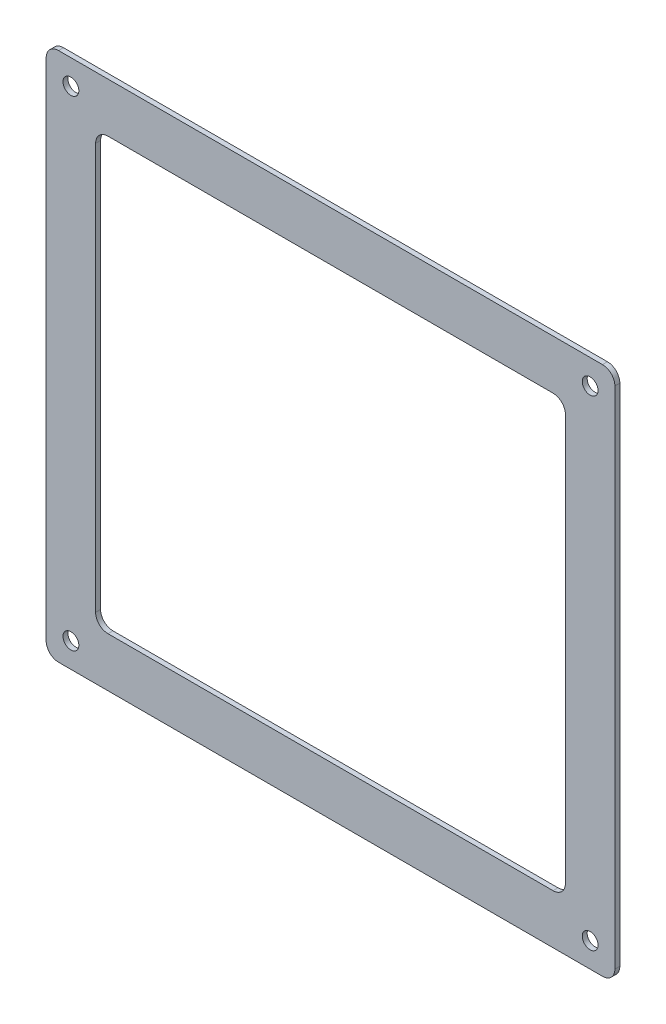
SolidWorks part; units mm, degrees
ref_plane "前视基准面" through (0, 0, 0) normal (0, 0, 1) x (1, 0, 0)
ref_plane "上视基准面" through (0, 0, 0) normal (0, 1, 0) x (1, 0, 0)
ref_plane "右视基准面" through (0, 0, 0) normal (1, 0, 0) x (0, 0, -1)
sketch "草图1" plane through (0, 0, 0) normal (0, 0, 1) x (1, 0, 0)
  line L1 (95, -87.125) -> (-95, -87.125)
  line L2 (95, -87.125) -> (95, 87.125)
  line L3 (95, 87.125) -> (-95, 87.125)
  line L4 (-95, -87.125) -> (-95, 87.125)
  line L5 (95, -87.125) -> (-95, 87.125) construction
  line L6 (95, 87.125) -> (-95, -87.125) construction
  line L7 (115, -107.125) -> (-115, -107.125)
  line L8 (115, -107.125) -> (115, 107.125)
  line L9 (115, 107.125) -> (-115, 107.125)
  line L10 (-115, -107.125) -> (-115, 107.125)
  line L11 (115, -107.125) -> (-115, 107.125) construction
  line L12 (115, 107.125) -> (-115, -107.125) construction
  point P0 (0, 0)
  point P6 (0, 0)
  dimension "D1" = 20
  dimension "D2" = 20
  dimension "D3" = 174.25
  dimension "D4" = 190
extrude "凸台-拉伸1" add sketch "草图1" along normal blind 2
fillet "圆角1" radius 5 8 edges at (95, -87.125, 1) (95, 87.125, 1) (-115, -107.125, 1) (-95, -87.125, 1) (-115, 107.125, 1) (-95, 87.125, 1) (115, -107.125, 1) (115, 107.125, 1)
sketch "草图2" plane through (0, 0, 2) normal (0, 0, 1) x (1, 0, 0)
  line L0 (-115, 102.125) -> (-115, -102.125) construction
  line L1 (110, 107.125) -> (-110, 107.125) construction
  line L2 (115, -102.125) -> (115, 102.125) construction
  line L3 (-110, -107.125) -> (110, -107.125) construction
  point P0 (-105, 97.125)
  point P1 (-105, -97.125)
  point P2 (105, -97.125)
  point P3 (105, 97.125)
  dimension "D1" = 10
  dimension "D2" = 10
  dimension "D3" = 10
  dimension "D4" = 10
  dimension "D5" = 10
  dimension "D6" = 10
  dimension "D7" = 10
  dimension "D8" = 10
hole_wizard "Ø6.4 (6.4) 直径孔1" positions "草图3" profile "草图4" hole size "Ø6.4" standard "GB" end condition through all
sketch "草图3" plane through (0, 0, 2) normal (0, 0, 1) x (1, 0, 0)
  point P0 (-105, 97.125)
  point P3 (-105, -97.125)
  point P6 (105, -97.125)
  point P9 (105, 97.125)
sketch "草图4" plane through (-105, 97.125, 2) normal (1, 0, 0) x (0, -1, 0)
  line L0 (0, 0) -> (0, 2)
  line L1 (0, 2) -> (3.2, 2)
  line L2 (3.2, 2) -> (3.2, 0)
  line L5 (3.2, 0) -> (0, 0)
  line L11 (0, -6.35) -> (0, 107.95) construction
  dimension "通孔孔直径" = 6.4
  dimension "通孔孔深度" = 2
